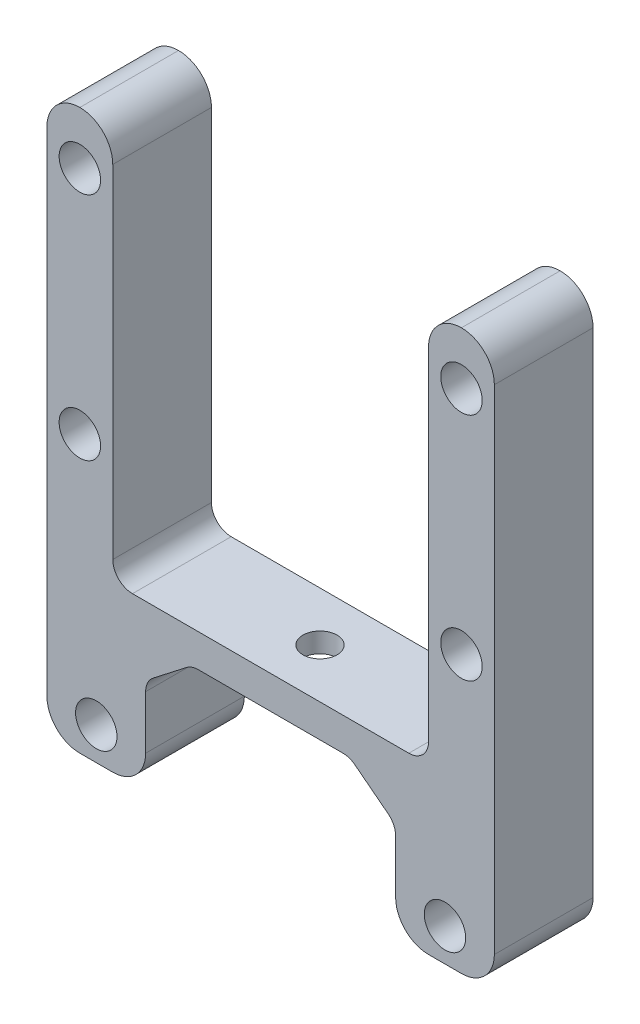
SolidWorks part; units mm, degrees
ref_plane "Plan de face" through (0, 0, 0) normal (0, 0, 1) x (1, 0, 0)
ref_plane "Plan de dessus" through (0, 0, 0) normal (0, 1, 0) x (1, 0, 0)
ref_plane "Plan de droite" through (0, 0, 0) normal (1, 0, 0) x (0, 0, -1)
sketch "Esquisse1" plane through (0, 0, 0) normal (0, 0, 1) x (1, 0, 0)
  line L0 (0, 0) -> (0, 5)
  line L1 (0, 5) -> (24, 5)
  line L2 (24, 5) -> (24, 65)
  line L3 (24, 65) -> (34, 65)
  line L4 (34, 65) -> (34, -20)
  line L5 (34, -20) -> (19, -20)
  line L6 (19, -20) -> (19, -5.4253)
  line L7 (19, -5.4253) -> (12, 0)
  line L8 (12, 0) -> (0, 0)
  circle A0 centre (29, 57) radius 3.15
  circle A1 centre (26.5, -15) radius 3.15
  circle A2 centre (29, 22) radius 3.15
  point P14 (0, 0)
  point P15 (29, 65)
  point P16 (26.5, -20)
  dimension "D5" = 6.3
  dimension "D1" = 24
  dimension "D2" = 60
  dimension "D3" = 10
  dimension "D4" = 5
  dimension "D6" = 8
  dimension "D7" = 5
  dimension "D8" = 15
  dimension "D9" = 25
  dimension "D10" = 35
extrude "Boss.-Extru.1" add sketch "Esquisse1" along normal blind 15
fillet "Congé1" radius 3 3 edges at (19, -5.4253, 7.5) (12, 0, 7.5) (24, 5, 7.5)
fillet "Congé2" radius 5 4 edges at (19, -20, 7.5) (34, -20, 7.5) (24, 65, 7.5) (34, 65, 7.5)
mirror "Symétrie2" about plane through (0, 0, 15) normal (1, 0, 0) of "Boss.-Extru.1", "Congé1", "Congé2"
sketch "Esquisse3" plane through (0, 0, 0) normal (0, -1, 0) x (1, 0, 0)
  line L0 (10.9735, 0) -> (10.9735, 15) construction
  circle A0 centre (0, 7.5) radius 5.75
  point P2 (0, 0)
  point P5 (10.9735, 7.5)
  point P6 (0, 7.5)
  dimension "D1" = 11.5
extrude "Enlèv. mat.-Extru.1" cut sketch "Esquisse3" against normal blind 2
sketch "Esquisse4" plane through (0, 2, 0) normal (0, -1, 0) x (1, 0, 0)
  circle A0 centre (0, 7.5) radius 2.6
  circle A1 centre (0, 7.5) radius 5.75 construction
  dimension "D1" = 5.2
extrude "Enlèv. mat.-Extru.2" cut sketch "Esquisse4" against normal up to next
mirror "Symétrie1"
